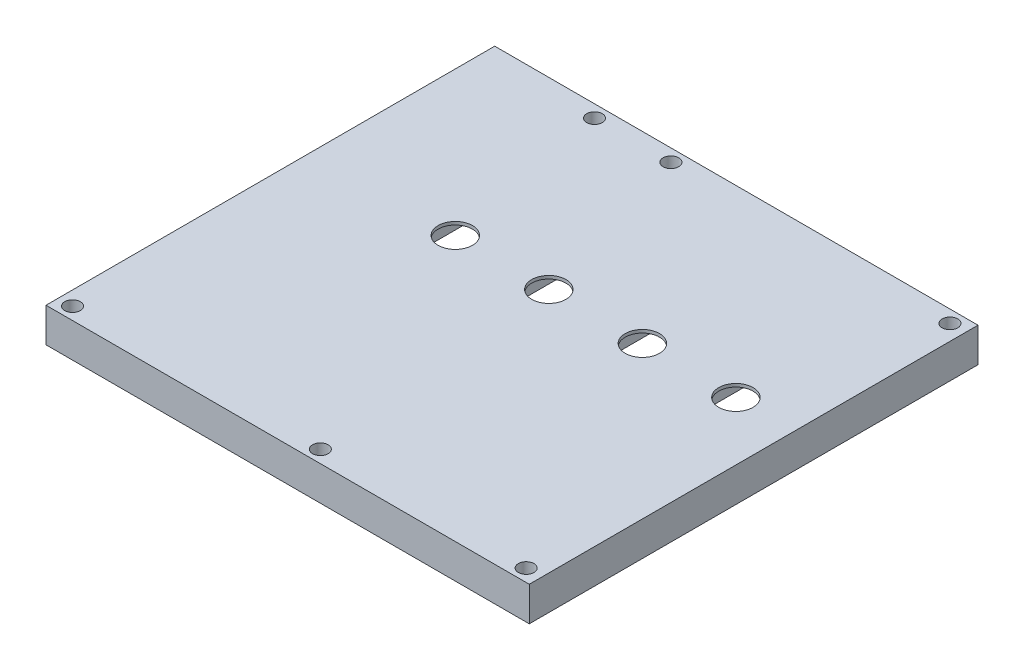
SolidWorks part; units mm, degrees
ref_plane "Front Plane" through (0, 0, 0) normal (0, 0, 1) x (1, 0, 0)
ref_plane "Top Plane" through (0, 0, 0) normal (0, 1, 0) x (1, 0, 0)
ref_plane "Right Plane" through (0, 0, 0) normal (1, 0, 0) x (0, 0, -1)
sketch "Sketch1" plane through (0, 0, 0) normal (0, 1, 0) x (1, 0, 0)
  line L1 (143.9586, 0) -> (298.9586, 0)
  line L2 (143.9586, 0) -> (143.9586, -143.9214)
  line L3 (143.9586, -143.9214) -> (298.9586, -143.9214)
  line L4 (298.9586, 0) -> (298.9586, -143.9214)
  dimension "D1" = 155
extrude "Boss-Extrude1" add sketch "Sketch1" along normal blind 11
sketch "Sketch2" plane through (0, 0, 0) normal (0, 1, 0) x (1, 0, 0)
  line L0 (298.9586, -143.9214) -> (298.9586, 0) construction
  line L1 (273.4586, 0) -> (216.4586, 0)
  line L2 (273.4586, 0) -> (273.4586, -20)
  line L3 (273.4586, -20) -> (216.4586, -20)
  line L4 (216.4586, 0) -> (216.4586, -20)
  dimension "D1" = 57
  dimension "D2" = 20
  dimension "D3" = 25.5
extrude "Cut-Extrude1" cut sketch "Sketch2" along normal blind 10
sketch "Sketch3" plane through (0, 0, 0) normal (0, 1, 0) x (1, 0, 0)
  line L3 (298.9586, -143.9214) -> (298.9586, 0) construction
  line L6 (292.7086, -20) -> (267.7086, -20)
  line L7 (292.7086, -20) -> (292.7086, -85.9)
  line L8 (292.7086, -85.9) -> (267.7086, -85.9)
  line L9 (267.7086, -20) -> (267.7086, -85.9)
  dimension "D1" = 65.9
  dimension "D5" = 6.25
  dimension "D6" = 25
extrude "Cut-Extrude2" cut sketch "Sketch3" along normal blind 10
pattern_linear "LPattern1" count 4 spacing 30 along (-1, 0, 0) of "Cut-Extrude2"
sketch "Sketch4" plane through (0, 0, 0) normal (0, 1, 0) x (1, 0, 0)
  line L1 (292.7086, -85.9) -> (292.7086, -20) construction
  line L2 (267.7086, -85.9) -> (292.7086, -85.9) construction
  circle A0 centre (280.2086, -58.9) radius 5.5
  dimension "D1" = 11
  dimension "D2" = 12.5
  dimension "D3" = 27
sketch "Sketch25" plane through (0, 0, 0) normal (0, 1, 0) x (1, 0, 0)
  line L0 (292.4586, -92.9) -> (296.9586, -98.538)
  line L1 (292.4586, -85.9) -> (287.9586, -85.9)
  line L2 (292.4586, -85.9) -> (292.4586, -92.9)
  line L3 (287.9586, -85.9) -> (287.9586, -92.9)
  line L4 (296.9586, -98.538) -> (296.9586, -108.788)
  line L5 (283.4586, -98.538) -> (283.4586, -108.788)
  line L6 (287.9586, -92.9) -> (283.4586, -98.538)
  line L8 (298.9586, -143.9214) -> (298.9586, 0) construction
  line L9 (284.7086, -117.788) -> (289.2086, -123.4259)
  line L10 (284.7086, -110.788) -> (280.2086, -110.788)
  line L11 (284.7086, -110.788) -> (284.7086, -117.788)
  line L12 (280.2086, -110.788) -> (280.2086, -117.788)
  line L13 (289.2086, -123.4259) -> (289.2086, -133.6759)
  line L14 (275.7086, -123.4259) -> (275.7086, -133.6759)
  line L15 (280.2086, -117.788) -> (275.7086, -123.4259)
  arc A0 (283.4586, -108.788) -> (296.9586, -108.788) centre (290.2086, -97.389) ccw
  arc A2 (275.7086, -133.6759) -> (289.2086, -133.6759) centre (282.4586, -122.2769) ccw
  dimension "D1" = 4.5
  dimension "D2" = 6.75
  dimension "D3" = 6.75
  dimension "D4" = 7.2136
  dimension "D5" = 4.5
  dimension "D6" = 4.5
  dimension "D7" = 13.5
  dimension "D8" = 10.25
  dimension "D9" = 10.25
  dimension "D10" = 7
  dimension "D11" = 2
  dimension "D13" = 4.5
  dimension "D14" = 6.75
  dimension "D15" = 6.75
  dimension "D16" = 4.5
  dimension "D17" = 4.5
  dimension "D18" = 7
  dimension "D19" = 10.25
  dimension "D20" = 10.25
  dimension "D21" = 13.5
  dimension "D22" = 7.2136
  dimension "D23" = 1.25
  dimension "D24" = 2
extrude "Cut-Extrude11" cut sketch "Sketch25" along normal blind 5
pattern_linear "LPattern3" count 8 spacing 15.5 along (-1, 0, 0) of "Cut-Extrude11"
sketch "Sketch27" plane through (0, 0, 0) normal (0, 1, 0) x (1, 0, 0)
  line L0 (284.7086, -110.788) -> (280.2086, -110.788) construction
  line L1 (283.4586, -85.9) -> (281.4586, -85.9)
  line L2 (283.4586, -85.9) -> (283.4586, -110.788)
  line L3 (283.4586, -110.788) -> (281.4586, -110.788)
  line L4 (281.4586, -85.9) -> (281.4586, -110.788)
  dimension "D1" = 2
  dimension "D2" = 1.25
extrude "Cut-Extrude14" cut sketch "Sketch27" along normal blind 2
pattern_linear "LPattern4" count 8 spacing 15.5 along (-1, 0, 0) of "Cut-Extrude14"
sketch "Sketch28" plane through (0, 0, 0) normal (0, 1, 0) x (1, 0, 0)
  line L0 (237.7086, -20) -> (237.7086, -85.9) construction
  line L3 (292.7086, -85.9) -> (292.7086, -20) construction
  line L4 (267.7086, -20) -> (267.7086, -85.9) construction
  circle A0 centre (295.2086, -35) radius 1.5
  circle A1 centre (295.2086, -65) radius 1.5
  circle A2 centre (265.2086, -65) radius 1.5
  circle A3 centre (265.2086, -35) radius 1.5
  circle A4 centre (265.2086, -42) radius 1.5
  circle A5 centre (265.2086, -72) radius 1.5
  circle A6 centre (235.2086, -42) radius 1.5
  circle A7 centre (235.2086, -72) radius 1.5
  dimension "D2" = 3
  dimension "D5" = 3
  dimension "D7" = 3
  dimension "D4" = 3
  dimension "D8" = 2.5
  dimension "D12" = 3
  dimension "D6" = 3
  dimension "D11" = 3
  dimension "D16" = 3
  dimension "D3" = 2.5
  dimension "D9" = 7
  dimension "D10" = 30
  dimension "D13" = 2.5
  dimension "D14" = 15
  dimension "D15" = 30
  dimension "D17" = 30
extrude "Cut-Extrude15" cut sketch "Sketch28" along normal blind 6
sketch "Sketch32" plane through (0, 0, 0) normal (0, 1, 0) x (1, 0, 0)
  line L1 (173.9586, 0) -> (143.9586, 0)
  line L2 (173.9586, 0) -> (173.9586, -35)
  line L3 (173.9586, -35) -> (143.9586, -35)
  line L4 (143.9586, 0) -> (143.9586, -35)
  dimension "D1" = 35
  dimension "D2" = 30
extrude "Cut-Extrude18" cut sketch "Sketch32" along normal blind 10
sketch "Sketch35" plane through (0, 0, 0) normal (0, 1, 0) x (1, 0, 0)
  line L0 (143.9586, -35) -> (143.9586, -143.9214) construction
  line L1 (173.9586, -35) -> (148.9586, -35)
  line L2 (164.9586, -52.9424) -> (164.9586, -130.7443)
  line L3 (164.9586, -130.7443) -> (148.9586, -130.7443)
  line L4 (148.9586, -52.9424) -> (148.9586, -130.7443)
  line L5 (148.9586, -52.9424) -> (148.9586, -35)
  line L6 (143.9586, -35) -> (173.9586, -35) construction
  line L7 (164.9586, -52.9424) -> (173.9586, -35)
  dimension "D1" = 5
  dimension "D2" = 16
extrude "Cut-Extrude21" cut sketch "Sketch35" along normal blind 9
sketch "Sketch36" plane through (0, 0, 0) normal (0, 1, 0) x (1, 0, 0)
  line L0 (164.9586, -130.7443) -> (164.9586, -52.9424) construction
  line L1 (148.9586, -35) -> (148.9586, -130.7443) construction
  circle A0 centre (167.9586, -93.538) radius 1.5
  circle A1 centre (146.4586, -93.538) radius 1.5
  circle A2 centre (146.4586, -55.37) radius 1.5
  circle A3 centre (167.9586, -55.37) radius 1.5
  dimension "D2" = 3
  dimension "D4" = 2.5
  dimension "D5" = 3
  dimension "D6" = 3
  dimension "D7" = 3
  dimension "D1" = 3
  dimension "D3" = 5
extrude "Cut-Extrude23" cut sketch "Sketch36" along normal blind 3
sketch "Sketch37" plane through (0, 0, 0) normal (0, 1, 0) x (1, 0, 0)
  line L0 (298.9586, -143.9214) -> (298.9586, 0) construction
  line L1 (143.9586, -35) -> (143.9586, -143.9214) construction
  line L3 (216.4586, 0) -> (216.4586, -20) construction
  line L4 (173.9586, -35) -> (173.9586, 0) construction
  line L9 (-6.05, 0) -> (6.05, 0) construction
  line L11 (143.9586, -143.9214) -> (298.9586, -143.9214) construction
  circle A0 centre (293.9586, -139.9214) radius 2.5
  circle A1 centre (148.4586, -139.9214) radius 2.5
  circle A2 centre (227.9586, -139.9214) radius 2.5
  circle A3 centre (293.9586, -4) radius 2.5
  circle A5 centre (204.4586, -4) radius 2.5
  circle A6 centre (179.9586, -4) radius 2.5
  dimension "D2" = 5
  dimension "D4" = 4.5
  dimension "D5" = 5
  dimension "D7" = 4
  dimension "D11" = 5
  dimension "D12" = 5
  dimension "D13" = 5
  dimension "D15" = 5
  dimension "D3" = 5
  dimension "D6" = 66
  dimension "D8" = 12
  dimension "D9" = 6
  dimension "D10" = 4
  dimension "D14" = 4
extrude "Cut-Extrude24" cut sketch "Sketch37" along normal blind 5
sketch "Sketch38" plane through (0, 0, 0) normal (0, 0, 1) x (1, 0, 0)
  line L0 (298.9586, 11) -> (298.9586, 0) construction
  circle A0 centre (285.9586, 5.8607) radius 3
  circle A1 centre (210.7138, 5.8607) radius 3
  circle A2 centre (186.9477, 5.8607) radius 3
  dimension "D1" = 6
  dimension "D2" = 13
extrude "Cut-Extrude25" cut sketch "Sketch38" along normal blind 6
extrude "Cut-Extrude28" cut sketch "Sketch4" along normal blind 11
pattern_linear "LPattern6" count 4 spacing 30 along (-1, 0, 0) of "Cut-Extrude28"
pattern_linear "LPattern8" count 2 spacing 60 along (-1, 0, 0) of "Cut-Extrude15"
extrude "Cut-Extrude29" cut sketch "Sketch37<2>" against normal blind 5 from surface starting at face at (220.2086, 11, 64.4)
sketch "Sketch37<2>" plane through (0, 0, 0) normal (0, 1, 0) x (1, 0, 0) same geometry as "Sketch37"
sketch "Sketch39" plane through (0, 0, 0) normal (0, 1, 0) x (1, 0, 0)
  line L0 (262.7086, -85.9) -> (262.7086, -20) construction
  line L1 (267.7086, -20) -> (262.7086, -20)
  line L2 (267.7086, -20) -> (267.7086, -31)
  line L3 (267.7086, -31) -> (262.7086, -31)
  line L4 (262.7086, -20) -> (262.7086, -31)
  dimension "D1" = 11
extrude "Cut-Extrude30" cut sketch "Sketch39" along normal blind 3
pattern_linear "LPattern9" count 3 spacing 30 along (-1, 0, 0) of "Cut-Extrude30"
sketch "Sketch40" plane through (0, 0, 0) normal (0, 1, 0) x (1, 0, 0)
  line L0 (267.7086, -31) -> (267.7086, -85.9) construction
  line L1 (267.7086, -76.9) -> (262.7086, -76.9)
  line L2 (267.7086, -76.9) -> (267.7086, -85.9)
  line L3 (267.7086, -85.9) -> (262.7086, -85.9)
  line L4 (262.7086, -76.9) -> (262.7086, -85.9)
  dimension "D1" = 9
extrude "Cut-Extrude31" cut sketch "Sketch40" along normal blind 2
pattern_linear "LPattern10" count 4 spacing 30 along (-1, 0, 0) of "Cut-Extrude31"
